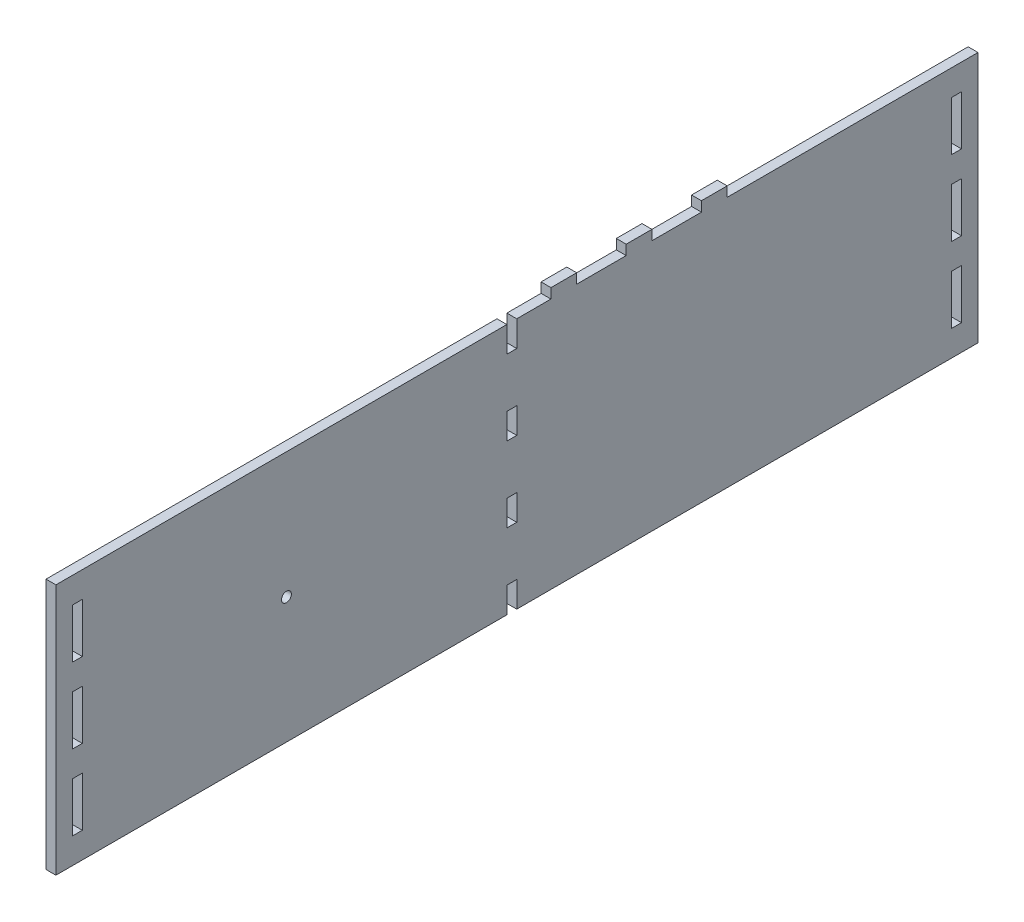
SolidWorks part; units mm, degrees
material "ENPH 253 Hardboard"
ref_plane "Front Plane" through (0, 0, 0) normal (0, 0, 1) x (1, 0, 0)
ref_plane "Top Plane" through (0, 0, 0) normal (0, 1, 0) x (1, 0, 0)
ref_plane "Right Plane" through (0, 0, 0) normal (1, 0, 0) x (0, 0, -1)
sketch "Sketch1" plane through (0, 0, 0) normal (1, 0, 0) x (0, 0, -1)
  line L1 (-139.7, 38.1) -> (139.7, 38.1)
  line L2 (-139.7, 38.1) -> (-139.7, -38.1)
  line L3 (-139.7, -38.1) -> (139.7, -38.1)
  line L4 (139.7, 38.1) -> (139.7, -38.1)
  line L5 (-139.7, 38.1) -> (139.7, -38.1) construction
  line L6 (-139.7, -38.1) -> (139.7, 38.1) construction
  point P0 (0, 0)
  dimension "D1" = 279.4
  dimension "D2" = 76.2
extrude "Boss-Extrude1" add sketch "Sketch1" against normal blind 3 contours L2 L3 L4 L1
sketch "Sketch3" plane through (-3, 0, 0) normal (-1, 0, 0) x (0, 0, 1)
  line L0 (-139.7, 38.1) -> (-139.7, -38.1) construction
  line L1 (139.7, 38.1) -> (139.7, -38.1) construction
  line L2 (139.7, 38.1) -> (-139.7, 38.1) construction
  line L3 (134.7, 30.3) -> (131.7, 30.3)
  line L4 (134.7, 30.3) -> (134.7, 15.3)
  line L5 (134.7, 15.3) -> (131.7, 15.3)
  line L6 (131.7, 30.3) -> (131.7, 15.3)
  line L7 (139.7, 38.1) -> (139.7, -38.1) construction
  circle A0 centre (69.85, 0) radius 50.8 construction
  circle A1 centre (-69.85, 0) radius 50.8 construction
  dimension "D1" = 101.6
  dimension "D2" = 101.6
  dimension "D3" = 69.85
  dimension "D4" = 69.85
  dimension "D5" = 15
  dimension "D6" = 7.8
  dimension "D7" = 5
  dimension "D8" = 3
extrude "Cut-Extrude1" cut sketch "Sketch3" against normal through all
pattern_linear "LPattern1" count 3 spacing 22.8 along (0, -1, 0) of "Cut-Extrude1"
mirror "Mirror1" about plane through (0, 0, 0) normal (0, 0, 1) of "LPattern1"
hole_wizard "Ø3.0mm Clearance Dowel Hole1" positions "Sketch4" profile "Sketch5" hole size "Ø3.0" standard "ANSI Metric" end condition through all
sketch "Sketch4" plane through (-3, 0, 0) normal (-1, 0, 0) x (0, 0, 1)
  point P3 (69.85, 0)
sketch "Sketch5" plane through (-3, 0, 69.85) normal (0, 1, 0) x (0, 0, 1)
  line L0 (0, 0) -> (0, 3)
  line L1 (0, 3) -> (1.5, 3)
  line L2 (1.5, 3) -> (1.5, 0)
  line L5 (1.5, 0) -> (0, 0)
  line L11 (0, -6.35) -> (0, 107.95) construction
  dimension "Thru Hole Dia." = 3
  dimension "Thru Hole Depth" = 3
sketch "Sketch6" plane through (-3, 0, 0) normal (-1, 0, 0) x (0, 0, 1)
  line L0 (139.7, 38.1) -> (-139.7, 38.1) construction
  line L1 (0.06, 38.1) -> (3.06, 38.1)
  line L2 (0.06, 38.1) -> (0.06, 30.3)
  line L3 (0.06, 30.3) -> (3.06, 30.3)
  line L4 (3.06, 38.1) -> (3.06, 30.3)
  dimension "D1" = 136.64
  dimension "D2" = 3
  dimension "D3" = 7.8
extrude "Cut-Extrude2" cut sketch "Sketch6" against normal through all
pattern_linear "LPattern2" count 4 spacing 22.8 along (0, -1, 0) of "Cut-Extrude2"
sketch "Sketch8" plane through (0, 38.1, 0) normal (0, 1, 0) x (1, 0, 0)
  line L0 (0, -139.7) -> (0, -3.06) construction
  line L1 (0, 18.1) -> (-3, 18.1)
  line L2 (0, 18.1) -> (0, 10.3)
  line L3 (0, 10.3) -> (-3, 10.3)
  line L4 (-3, 18.1) -> (-3, 10.3)
  line L5 (-3, -139.7) -> (-3, -3.06) construction
  line L6 (-3, -139.7) -> (0, -139.7) construction
  point P10 (-1.5, -139.7)
  dimension "D1" = 150
  dimension "D2" = 7.8
extrude "Boss-Extrude2" add sketch "Sketch8" along normal blind 3
pattern_linear "LPattern4" count 3 spacing 22.8 along (0, 0, -1) of "Boss-Extrude2"
equation "\"D4@Sketch3\"=\"D3@Sketch3\""
